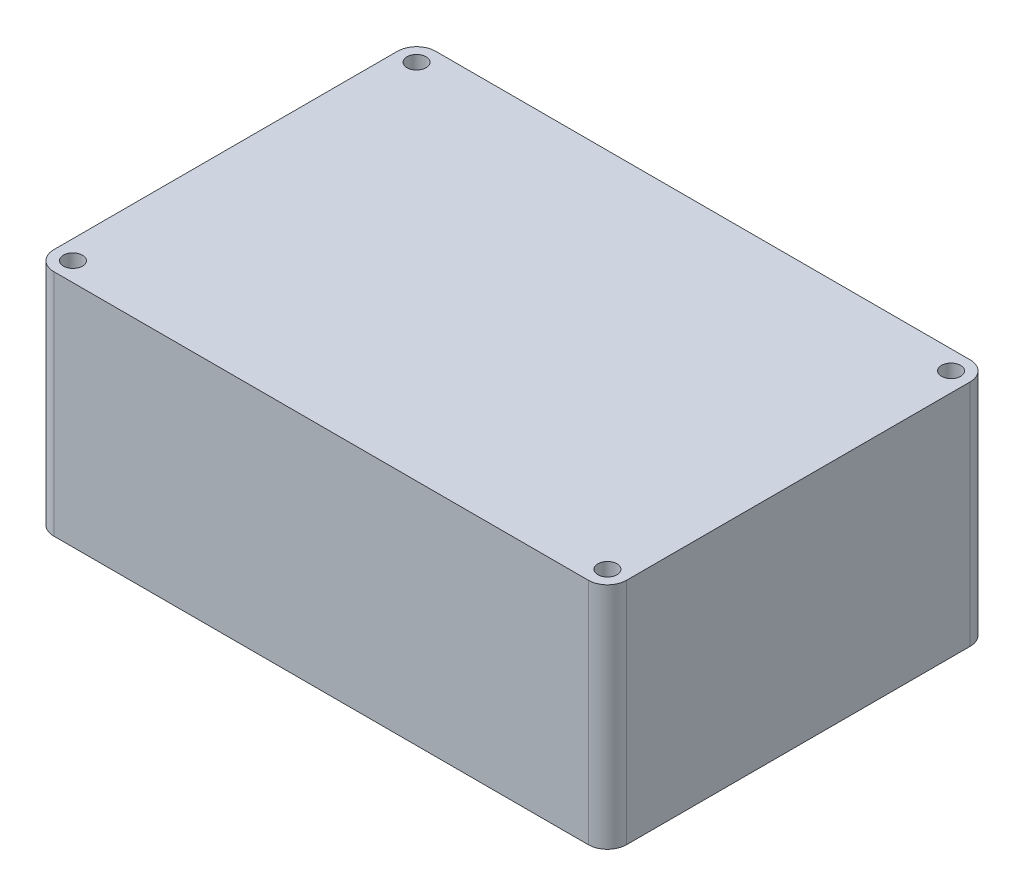
SolidWorks part; units mm, degrees
ref_plane "Alzado" through (0, 0, 0) normal (0, 0, 1) x (1, 0, 0)
ref_plane "Planta" through (0, 0, 0) normal (0, 1, 0) x (1, 0, 0)
ref_plane "Vista lateral" through (0, 0, 0) normal (1, 0, 0) x (0, 0, -1)
sketch "Croquis1" plane through (0, 0, 0) normal (0, 1, 0) x (1, 0, 0)
  line L0 (0, 100) -> (0, -100) construction
  line L1 (-150, 100) -> (150, 100)
  line L2 (-150, 100) -> (-150, -100)
  line L3 (-150, -100) -> (150, -100)
  line L4 (150, 100) -> (150, -100)
  dimension "D1" = 300
  dimension "D2" = 200
extrude "Saliente-Extruir1" add sketch "Croquis1" along normal blind 120
fillet "Redondeo1" radius 10 4 edges at (-150, 60, -100) (150, 60, -100) (150, 60, 100) (-150, 60, 100)
sketch "Croquis2" plane through (0, 120, 0) normal (0, 1, 0) x (1, 0, 0)
  circle A0 centre (-140, 90) radius 5
  dimension "D1" = 10
extrude "Cortar-Extruir1" cut sketch "Croquis2" against normal through all
mirror "Simetría1" about plane through (0, 0, 0) normal (0, 0, 1) of "Cortar-Extruir1" second plane through (0, 0, 0) second plane normal (1, 0, 0)
equation "\"Width\" = 300.0"
equation "\"Depth\" = 200.0"
equation "\"Height\" = 120.0"
equation "\"D1@Croquis1\"=\"Width\""
equation "\"D2@Croquis1\"=\"Depth\""
equation "\"D1@Saliente-Extruir1\"=\"Height\""
